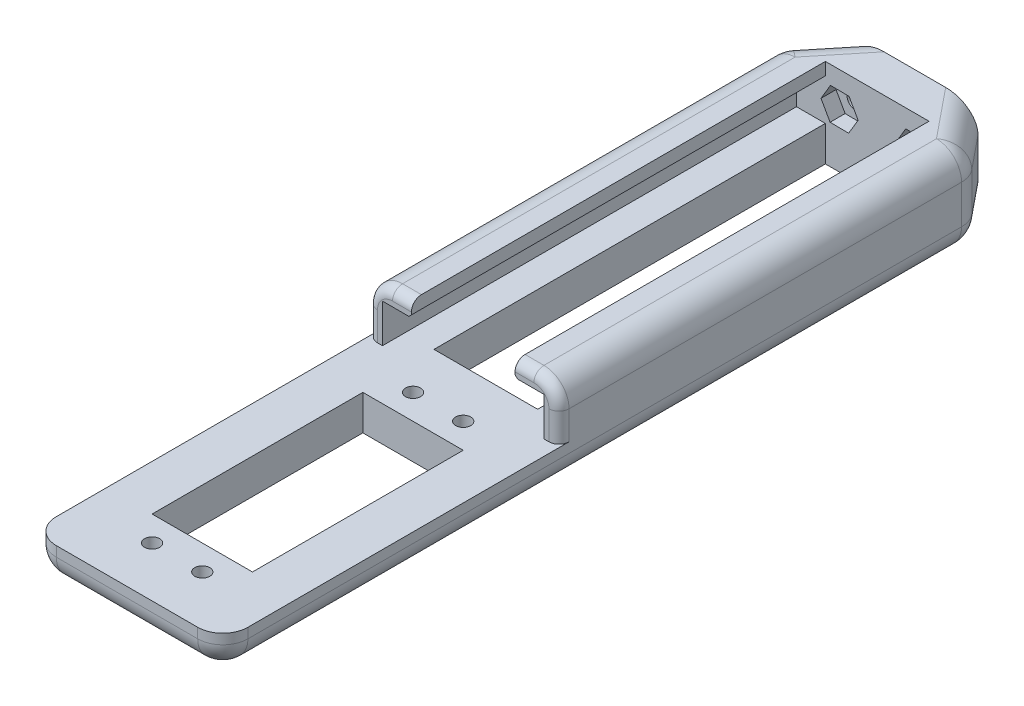
SolidWorks part; units mm, degrees
ref_plane "Front Plane" through (0, 0, 0) normal (0, 0, 1) x (1, 0, 0)
ref_plane "Top Plane" through (0, 0, 0) normal (0, 1, 0) x (1, 0, 0)
ref_plane "Right Plane" through (0, 0, 0) normal (1, 0, 0) x (0, 0, -1)
sketch "Sketch1" plane through (0, 0, 0) normal (0, 0, 1) x (1, 0, 0)
  line L0 (-69.7691, 23.4512) -> (-75.5286, 23.4512)
  line L1 (-75.5286, 23.4512) -> (-75.5286, 15.7512)
  line L2 (-75.5286, 15.7512) -> (-69.7691, 15.7512)
  line L3 (-69.7691, 15.7512) -> (-69.7691, 8.7512)
  line L4 (-69.7691, 8.7512) -> (-78.5286, 8.7512)
  line L5 (-78.5286, 8.7512) -> (-78.5286, 26.4512)
  line L6 (-78.5286, 26.4512) -> (-69.7691, 26.4512)
  line L7 (-69.7691, 26.4512) -> (-69.7691, 23.4512)
  line L8 (-49.1122, 23.4512) -> (-49.1122, 26.4512)
  line L9 (-49.1122, 26.4512) -> (-40.3527, 26.4512)
  line L10 (-40.3527, 26.4512) -> (-40.3527, 8.7512)
  line L11 (-40.3527, 8.7512) -> (-49.1122, 8.7512)
  line L12 (-49.1122, 8.7512) -> (-49.1122, 15.7512)
  line L13 (-49.1122, 15.7512) -> (-43.3527, 15.7512)
  line L14 (-43.3527, 15.7512) -> (-43.3527, 23.4512)
  line L15 (-43.3527, 23.4512) -> (-49.1122, 23.4512)
  dimension "D1" = 17.7
  dimension "D2" = 5.7594
  dimension "D3" = 20.657
  dimension "D4" = 7.7
  dimension "D8" = 3
  dimension "D9" = 3
extrude "Boss-Extrude1" add sketch "Sketch1" along normal blind 55 and the other way blind 35
sketch "Sketch2" plane through (0, 26.4512, 0) normal (0, 1, 0) x (1, 0, 0)
  line L0 (-40.3527, 35) -> (-40.3527, -55) construction
  line L6 (-78.5286, 35) -> (-40.3527, 35)
  line L7 (-78.5286, 35) -> (-78.5286, 27.5)
  line L8 (-78.5286, 27.5) -> (-40.3527, 27.5)
  line L9 (-40.3527, 35) -> (-40.3527, 27.5)
  dimension "D1" = 7.5
extrude "Boss-Extrude2" add sketch "Sketch2" against normal up to vertex (3 mm away) up to point (-69.7691, 23.4512, -35)
sketch "Sketch3" plane through (0, 8.7512, 0) normal (0, -1, 0) x (1, 0, 0)
  line L0 (-40.3527, -35) -> (-40.3527, 55) construction
  line L1 (-78.5286, 55) -> (-40.3527, 55)
  line L2 (-78.5286, 55) -> (-78.5286, 47.5)
  line L3 (-78.5286, 47.5) -> (-40.3527, 47.5)
  line L4 (-40.3527, 55) -> (-40.3527, 47.5)
  line L6 (-78.5286, -35) -> (-40.3527, -35)
  line L7 (-78.5286, -35) -> (-78.5286, -27.5)
  line L8 (-78.5286, -27.5) -> (-40.3527, -27.5)
  line L9 (-40.3527, -35) -> (-40.3527, -27.5)
  line L10 (-69.7691, -27.5) -> (-49.1122, -27.5) construction
extrude "Boss-Extrude3" add sketch "Sketch3" against normal up to vertex (7 mm away) up to point (-69.7691, 15.7512, 55)
ref_plane "MidSlide" through (0, 19.6012, 0) normal (0, 1, 0) x (1, 0, 0)
ref_plane "Plane2" through (-59.4407, 0, 0) normal (1, 0, 0) x (0, 0, -1)
sketch "Sketch11" plane through (0, 15.7512, 0) normal (0, 1, 0) x (1, 0, 0)
  line L0 (-49.4407, -86) -> (-40.3527, -86) construction
  line L1 (-40.3527, -122) -> (-78.5286, -122)
  line L2 (-40.3527, -122) -> (-40.3527, -55)
  line L3 (-40.3527, -55) -> (-78.5286, -55)
  line L4 (-78.5286, -122) -> (-78.5286, -55)
  line L5 (-49.4407, -107) -> (-69.4407, -107)
  line L6 (-49.4407, -107) -> (-49.4407, -65)
  line L7 (-49.4407, -65) -> (-69.4407, -65)
  line L8 (-69.4407, -107) -> (-69.4407, -65)
  line L9 (-69.4407, -86) -> (-78.5286, -86) construction
  line L10 (-59.4407, -107) -> (-59.4407, -122) construction
  line L11 (-49.4407, -65) -> (-49.4407, -60) construction
  line L12 (-54.4407, -60) -> (-54.4407, -65) construction
  line L13 (-54.4407, -112) -> (-54.4407, -107) construction
  line L14 (-49.4407, -60) -> (-54.4407, -60) construction
  line L15 (-54.4407, -60) -> (-64.4407, -60) construction
  line L16 (-64.4407, -60) -> (-69.4407, -60) construction
  line L17 (-69.4407, -60) -> (-69.4407, -65) construction
  line L18 (-78.5286, -55) -> (-40.3527, -55) construction
  line L19 (-59.4407, -9.735) -> (-59.4407, 9.735) construction
  line L20 (-43.3527, -55) -> (-75.5286, -55) construction
  line L21 (-78.5286, 35) -> (-78.5286, -55) construction
  circle A0 centre (-54.4407, -112) radius 1.5
  circle A1 centre (-64.4407, -112) radius 1.5
  circle A2 centre (-54.4407, -60) radius 1.5
  circle A3 centre (-64.4407, -60) radius 1.5
  point P28 (-59.4407, -55)
  dimension "D5" = 10
  dimension "D4" = 3
  dimension "D1" = 10
  dimension "D2" = 20
  dimension "D3" = 42
  dimension "D6" = 5
  dimension "D7" = 15
extrude "Boss-Extrude7" add sketch "Sketch11" against normal blind 7
sketch "Sketch6" plane through (0, 0, -35) normal (0, 0, -1) x (-1, 0, 0)
  line L1 (43.3527, 23.4512) -> (75.5286, 23.4512)
  line L2 (43.3527, 23.4512) -> (43.3527, 15.7512)
  line L3 (43.3527, 15.7512) -> (75.5286, 15.7512)
  line L4 (75.5286, 23.4512) -> (75.5286, 15.7512)
  line L6 (43.3527, 23.4512) -> (43.3527, 15.7512) construction
  line L7 (43.3527, 15.7512) -> (75.5286, 15.7512) construction
  line L8 (75.5286, 23.4512) -> (43.3527, 23.4512) construction
  line L9 (75.5286, 15.7512) -> (75.5286, 23.4512) construction
sketch "Sketch7" plane through (0, 0, -35) normal (0, 0, -1) x (-1, 0, 0)
  line L0 (78.5286, 8.7512) -> (78.5286, 26.4512) construction
  line L1 (78.5286, 26.4512) -> (40.3527, 26.4512) construction
  line L2 (40.3527, 8.7512) -> (40.3527, 26.4512) construction
  line L3 (40.3527, 26.4512) -> (78.5286, 26.4512) construction
  line L4 (40.3527, 26.4512) -> (40.3527, 8.7512) construction
  line L5 (40.3527, 8.7512) -> (78.5286, 8.7512) construction
  line L6 (75.5286, 15.7512) -> (75.5286, 23.4512) construction
  line L7 (75.5286, 19.6012) -> (66.9407, 19.6012) construction
  line L8 (75.5286, 23.4512) -> (43.3527, 23.4512) construction
  line L9 (51.9407, 19.6012) -> (43.3527, 19.6012) construction
  line L10 (43.3527, 23.4512) -> (43.3527, 15.7512) construction
  circle A0 centre (66.9407, 19.6012) radius 1.5
  circle A1 centre (51.9407, 19.6012) radius 1.5
  dimension "D2" = 3
  dimension "D1" = 15
sketch "Sketch9" plane through (0, 26.4512, 0) normal (0, 1, 0) x (1, 0, 0)
  line L0 (-72.0286, 35) -> (-78.5286, 35)
  line L1 (-40.3527, 35) -> (-78.5286, 35) construction
  line L2 (-78.5286, 35) -> (-78.5286, 27)
  line L3 (-78.5286, 35) -> (-78.5286, -55) construction
  line L4 (-78.5286, 27) -> (-72.0286, 35)
  line L5 (-46.8527, 35) -> (-40.3527, 35)
  line L6 (-40.3527, 35) -> (-40.3527, 27)
  line L7 (-40.3527, -55) -> (-40.3527, 35) construction
  line L8 (-40.3527, 27) -> (-46.8527, 35)
  dimension "D1" = 8
  dimension "D2" = 6.5
ref_plane "Plane3" through (-40.3527, 26.4512, -35) normal (0, 0, -1) x (-1, 0, 0)
extrude "Boss-Extrude8" add sketch "Sketch6" against normal blind 7.5
extrude "Cut-Extrude1" cut sketch "Sketch9" against normal blind 18
extrude "Cut-Extrude2" cut sketch "Sketch7" against normal blind 10
sketch "Sketch14" plane through (0, 0, -27.5) normal (0, 0, 1) x (1, 0, 0)
  line L1 (-65.0515, 22.7829) -> (-68.7515, 22.8281)
  line L2 (-68.7515, 22.8281) -> (-70.6407, 19.6464)
  line L3 (-70.6407, 19.6464) -> (-68.8298, 16.4195)
  line L4 (-68.8298, 16.4195) -> (-65.1298, 16.3743)
  line L5 (-65.1298, 16.3743) -> (-63.2407, 19.556)
  line L6 (-63.2407, 19.556) -> (-65.0515, 22.7829)
  line L7 (-55.6407, 19.6464) -> (-53.8298, 16.4195)
  line L8 (-53.8298, 16.4195) -> (-50.1298, 16.3743)
  line L9 (-50.1298, 16.3743) -> (-48.2407, 19.556)
  line L10 (-48.2407, 19.556) -> (-50.0515, 22.7829)
  line L11 (-50.0515, 22.7829) -> (-53.7515, 22.8281)
  line L12 (-53.7515, 22.8281) -> (-55.6407, 19.6464)
  circle A0 centre (-66.9407, 19.6012) radius 3.2045 construction
  circle A1 centre (-51.9407, 19.6012) radius 3.2045 construction
  dimension "D1" = 3.7
extrude "Cut-Extrude3" cut sketch "Sketch14" against normal blind 3
chamfer "Chamfer1" distance 0.5 angle 45 2 edges at (-69.7691, 23.4512, 13.75) (-49.1122, 23.4512, 13.75)
chamfer "Chamfer2" distance 10 angle 45 1 edges at (-59.4407, 8.7512, 47.5)
fillet "Fillet38" radius 5 4 edges at (-40.3527, 8.7512, 47.5) (-78.5286, 26.4512, 14) (-40.3527, 26.4512, 14) (-78.5286, 8.7512, 47.5)
fillet "Fillet39" radius 5 5 edges at (-77.0641, 10.2156, 122) (-59.4407, 8.7512, 122) (-41.8172, 10.2156, 122) (-78.5286, 14.7512, 122) (-40.3527, 14.7512, 122)
fillet "Fillet40" radius 2 5 edges at (-47.2324, 26.4512, 55) (-77.0641, 24.9867, 55) (-41.8172, 24.9867, 55)
fillet "Fillet41" radius 5 10 edges at (-72.7786, 8.7512, -34.0769) (-77.0641, 10.2156, -28.8024) (-78.5286, 17.6012, -27) (-72.7786, 26.4512, -34.0769) (-46.1027, 26.4512, -34.0769) (-46.1027, 8.7512, -34.0769) (-41.8172, 10.2156, -28.8024) (-40.3527, 17.6012, -27) (-77.0641, 24.9867, -28.8024) (-41.8172, 24.9867, -28.8024)
